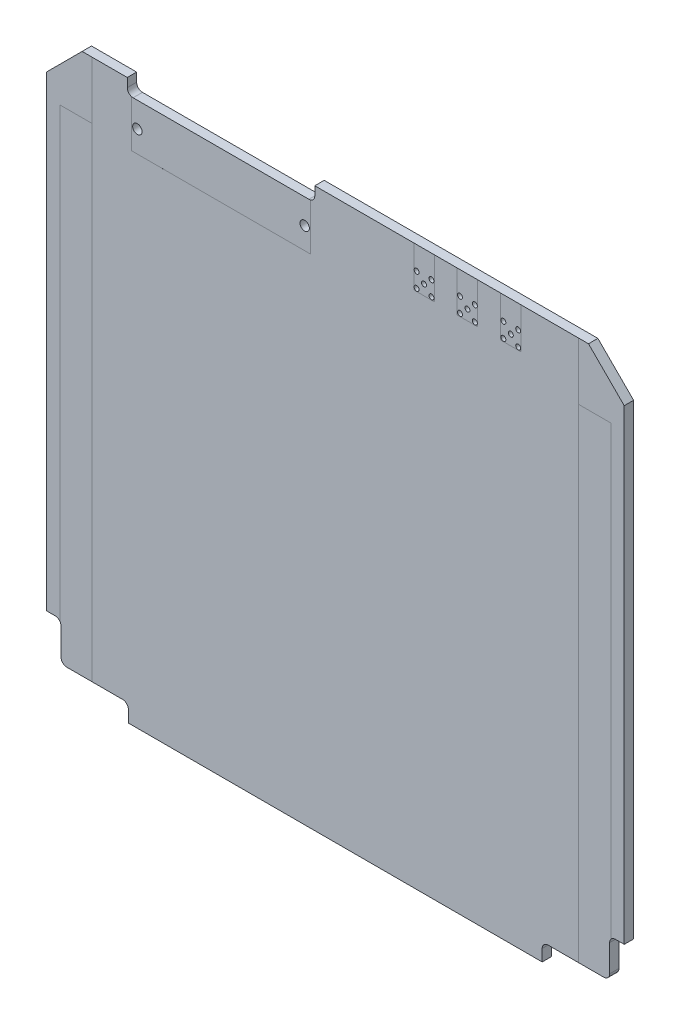
SolidWorks part; units mm, degrees
material "Oshpark board"
ref_plane "Front Plane" through (0, 0, 0) normal (0, 0, 1) x (1, 0, 0)
ref_plane "Top Plane" through (0, 0, 0) normal (0, 1, 0) x (1, 0, 0)
ref_plane "Right Plane" through (0, 0, 0) normal (1, 0, 0) x (0, 0, -1)
ref_plane "Plane4" through (0, 0, -0.0125) normal (0, 0, -1) x (-1, 0, 0)
sketch "Sketch1" plane through (0, 0, -0.0125) normal (0, 0, -1) x (-1, 0, 0)
  line L0 (35.3, -50) -> (35.3, -48)
  line L1 (36.3, -47) -> (45.8, -47)
  line L2 (46.8, -46) -> (46.8, -41.4)
  line L3 (47.8, -40.4) -> (49.3, -40.4)
  line L4 (49.3, -40.4) -> (49.3, 39.2)
  line L5 (49.3, 39.2) -> (43.2, 45.3)
  line L6 (43.2, 45.3) -> (35.5, 45.3)
  line L7 (35.5, 45.3) -> (35.5, 43.8)
  line L8 (34.5, 42.8) -> (4.5, 42.8)
  line L9 (3.5, 43.8) -> (3.5, 45.3)
  line L10 (3.5, 45.3) -> (-43.2, 45.3)
  line L11 (-43.2, 45.3) -> (-49.3, 39.2)
  line L12 (-49.3, 39.2) -> (-49.3, -40.4)
  line L13 (-49.3, -40.4) -> (-47.8, -40.4)
  line L14 (-46.8, -41.4) -> (-46.8, -46)
  line L15 (-45.8, -47) -> (-36.3, -47)
  line L16 (-35.3, -48) -> (-35.3, -50)
  line L17 (-35.3, -50) -> (35.3, -50)
  line L18 (0, -50) -> (0, 45.3) construction
  line L19 (19.5, 42.8) -> (19.5, 25.5258) construction
  line L20 (-13.87, 41.37) -> (-16.41, 38.83) construction
  line L21 (-21.27, 41.37) -> (-23.81, 38.83) construction
  line L22 (-28.67, 41.37) -> (-31.21, 38.83) construction
  arc A0 (35.3, -48) -> (36.3, -47) centre (36.3, -48) cw
  arc A1 (45.8, -47) -> (46.8, -46) centre (45.8, -46) ccw
  arc A2 (46.8, -41.4) -> (47.8, -40.4) centre (47.8, -41.4) cw
  arc A3 (35.5, 43.8) -> (34.5, 42.8) centre (34.5, 43.8) cw
  arc A4 (4.5, 42.8) -> (3.5, 43.8) centre (4.5, 43.8) cw
  arc A5 (-47.8, -40.4) -> (-46.8, -41.4) centre (-47.8, -41.4) cw
  arc A6 (-46.8, -46) -> (-45.8, -47) centre (-45.8, -46) ccw
  arc A7 (-36.3, -47) -> (-35.3, -48) centre (-36.3, -48) cw
  circle A8 centre (-21.27, 41.37) radius 0.425
  circle A9 centre (-23.81, 41.37) radius 0.425
  circle A10 centre (-22.54, 40.1) radius 0.425
  circle A11 centre (-13.87, 41.37) radius 0.425
  circle A12 centre (-23.81, 38.83) radius 0.425
  circle A13 centre (-16.41, 41.37) radius 0.425
  circle A14 centre (-15.14, 40.1) radius 0.425
  circle A15 centre (-21.27, 38.83) radius 0.425
  circle A16 centre (-28.67, 41.37) radius 0.425
  circle A17 centre (-31.21, 41.37) radius 0.425
  circle A18 centre (-16.41, 38.83) radius 0.425
  circle A19 centre (-29.94, 40.1) radius 0.425
  circle A20 centre (-31.21, 38.83) radius 0.425
  circle A21 centre (-28.67, 38.83) radius 0.425
  circle A22 centre (33.775, 38.54) radius 0.8
  circle A23 centre (5.225, 38.54) radius 0.8
  circle A24 centre (-13.87, 38.83) radius 0.425
  point P35 (-15.14, 40.1)
  dimension "D7" = 2.5
  dimension "D8" = 1.6
  dimension "D9" = 14.275
  dimension "D10" = 4.26
  dimension "D11" = 1
  dimension "D12" = 1
  dimension "D13" = 1
  dimension "D14" = 1
  dimension "D15" = 1
  dimension "D16" = 1
  dimension "D17" = 1
  dimension "D18" = 1
  dimension "D26" = 0.85
  dimension "D1" = 98.6
  dimension "D2" = 95.3
  dimension "D3" = 14
  dimension "D4" = 9.6
  dimension "D5" = 2.5
  dimension "D6" = 3
  dimension "D19" = 14
  dimension "D20" = 2.5
  dimension "D21" = 6.1
  dimension "D22" = 6.1
  dimension "D23" = 32
  dimension "D24" = 2.54
  dimension "D25" = 2.54
  dimension "D28" = 7.4
  dimension "D29" = 3.93
  dimension "D30" = 35.43
  dimension "D31" = 45
  dimension "D32" = 45
  dimension "D33" = 29.8
  dimension "D34" = 50
  dimension "D27" = 3
extrude "Boss-Extrude1" add sketch "Sketch1" against normal blind 1.6
sketch "thermalContacts_lower" plane through (0, 0, -0.0125) normal (0, 0, -1) x (-1, 0, 0)
  line L3 (47, 35.5) -> (47, -41.5)
  line L4 (41.5, 35.5) -> (41.5, 41.5)
  line L5 (41.5, 35.5) -> (47, 35.5)
  line L9 (-47, 35.5) -> (-47, -41.1726)
  line L10 (-41.5, 35.5) -> (-47, 35.5)
  line L11 (-41.5, 35.5) -> (-41.5, 42.5522)
  line L14 (-41.5, 42.5522) -> (-41.5, 47.8583)
  line L18 (41.5, 41.5) -> (41.5, 47)
  line L20 (47, -41.5) -> (59.8273, -41.5)
  line L21 (59.8273, -41.5) -> (59.8273, 47)
  line L22 (-54.1782, 47.8583) -> (-41.5, 47.8583)
  line L23 (41.5, 47) -> (59.8273, 47)
  line L24 (-54.1782, 47.8583) -> (-54.1782, -41.1726)
  line L25 (-47, -41.1726) -> (-54.1782, -41.1726)
  line L26 (43.2, 45.3) -> (35.5, 45.3) construction
  line L27 (49.3, -40.4) -> (49.3, 39.2) construction
  line L28 (3.5, 45.3) -> (-43.2, 45.3) construction
  line L29 (-49.3, 39.2) -> (-49.3, -40.4) construction
  dimension "D1" = 9.8
  dimension "D2" = 7.8
  dimension "D3" = 2.3
  dimension "D4" = 9.8
  dimension "D5" = 7.8
  dimension "D6" = 2.3
sketch "thermalContacts_upper" plane through (0, 0, 1.5875) normal (0, 0, 1) x (1, 0, 0)
  line L3 (-47, 35.5) -> (-47, -41.5)
  line L4 (-41.5, 35.5) -> (-41.5, 41.5)
  line L5 (-41.5, 35.5) -> (-47, 35.5)
  line L9 (47, 35.5) -> (47, -41.5)
  line L10 (41.5, 35.5) -> (47, 35.5)
  line L11 (41.5, 35.5) -> (41.5, 41.5)
  line L14 (41.5, 41.5) -> (41.5, 47)
  line L15 (41.5, 41.5) -> (49.5, 41.5) construction
  line L18 (-41.5, 41.5) -> (-41.5, 47)
  line L19 (-41.5, 41.5) -> (-49.5, 41.5) construction
  line L20 (47, -41.5) -> (59.8273, -41.5)
  line L21 (59.8273, -41.5) -> (59.8273, 47)
  line L22 (59.8273, 47) -> (41.5, 47)
  line L23 (-41.5, 47) -> (-56.1922, 47)
  line L24 (-56.1922, 47) -> (-56.1922, -41.5)
  line L25 (-56.1922, -41.5) -> (-47, -41.5)
extrude "keepOut_top" cut sketch "thermalContacts_lower" against normal blind 0.0001
extrude "keepOut_bottom" cut sketch "thermalContacts_upper" against normal blind 0.0001
sketch "partFootprints" plane through (0, 0, 1.5875) normal (0, 0, 1) x (1, 0, 0)
  line L0 (-34.74, 34.84) -> (-34.74, 42.8292)
  line L1 (-4.26, 34.84) -> (-34.74, 34.84)
  line L2 (-41.5, 45.3) -> (-35.5, 45.3) construction
  line L3 (-36.1132, 45.3) -> (-39.5054, 45.3) construction
  line L4 (-4.26, 34.84) -> (-4.26, 42.8292)
  line L5 (-49.3, -40.4) -> (-49.3, 39.2) construction
  line L6 (13.39, 45.3) -> (13.39, 38.35)
  line L7 (13.39, 38.35) -> (16.89, 38.35)
  line L8 (16.89, 38.35) -> (16.89, 45.3)
  line L9 (16.89, 45.3) -> (13.39, 45.3)
  line L10 (20.79, 45.3) -> (20.79, 38.35)
  line L11 (20.79, 38.35) -> (24.29, 38.35)
  line L12 (24.29, 38.35) -> (24.29, 45.3)
  line L13 (24.29, 45.3) -> (20.79, 45.3)
  line L14 (28.19, 45.3) -> (28.19, 38.35)
  line L15 (28.19, 38.35) -> (31.69, 38.35)
  line L16 (31.69, 38.35) -> (31.69, 45.3)
  line L17 (31.69, 45.3) -> (28.19, 45.3)
  line L18 (49.3, -40.4) -> (49.3, 39.2) construction
  line L20 (-34.74, 42.8292) -> (-4.26, 42.8292)
  line L21 (-3.5, 45.3) -> (41.5, 45.3) construction
  line L22 (14.12, 38.35) -> (15.8235, 38.35) construction
  line L25 (13.39, 42.2411) -> (13.39, 38.35) construction
  line L26 (16.89, 41.85) -> (16.89, 38.35) construction
  arc A0 (-35.5, 43.8) -> (-34.5, 42.8) centre (-34.5, 43.8) ccw construction
  arc A1 (-4.5, 42.8) -> (-3.5, 43.8) centre (-4.5, 43.8) ccw construction
  dimension "D1" = 10.46
  dimension "D2" = 14.56
  dimension "D3" = 30.48
  dimension "D4" = 6.95
  dimension "D5" = 17.61
  dimension "D7" = 7.4
  dimension "D8" = 3.5
  dimension "D6" = 3
extrude "footPrints" cut sketch "partFootprints" against normal blind 0.0001
sketch "Sketch3" plane through (0, 0, 1.5875) normal (0, 0, 1) x (1, 0, 0)
  line L1 (41.5, -47) -> (41.5, 35.5)
  line L2 (47, 35.5) -> (47, -40.8) construction
  line L3 (46.8, -41.4) -> (46.8, -46) construction
  line L4 (45.8, -47) -> (36.3, -47) construction
  line L5 (47, 35.5) -> (47, -40.8)
  line L6 (46.8, -41.4) -> (46.8, -46)
  line L7 (45.8, -47) -> (41.5, -47)
  line L8 (41.5, 35.5) -> (47, 35.5) construction
  line L9 (41.5, 35.5) -> (47, 35.5)
  line L10 (0, -50) -> (0, 45.3) construction
  line L11 (35.3, -50) -> (-35.3, -50) construction
  line L12 (-3.5, 45.3) -> (13.39, 45.3) construction
  line L13 (-41.5, 35.5) -> (-47, 35.5)
  line L14 (-45.8, -47) -> (-41.5, -47)
  line L15 (-46.8, -41.4) -> (-46.8, -46)
  line L16 (-47, 35.5) -> (-47, -40.8)
  line L17 (-41.5, -47) -> (-41.5, 35.5)
  line L18 (41.5, 45.3) -> (41.5, 35.5) construction
  arc A0 (47, -40.8) -> (46.8, -41.4) centre (47.8, -41.4) ccw construction
  arc A1 (45.8, -47) -> (46.8, -46) centre (45.8, -46) ccw construction
  arc A2 (47, -40.8) -> (46.8, -41.4) centre (47.8, -41.4) ccw
  arc A3 (45.8, -47) -> (46.8, -46) centre (45.8, -46) ccw
  arc A4 (-45.8, -47) -> (-46.8, -46) centre (-45.8, -46) cw
  arc A5 (-47, -40.8) -> (-46.8, -41.4) centre (-47.8, -41.4) cw
  point P28 (0, 0)
extrude "caution_top" cut sketch "Sketch3" against normal blind 0.0001
ref_plane "midplane_Z" through (0, 0, 0.7875) normal (0, 0, 1) x (1, 0, 0)
mirror "caution_bottom" about plane through (0, 0, 0.7875) normal (0, 0, 1) of "caution_top"
ref_point "rail midpoint"
